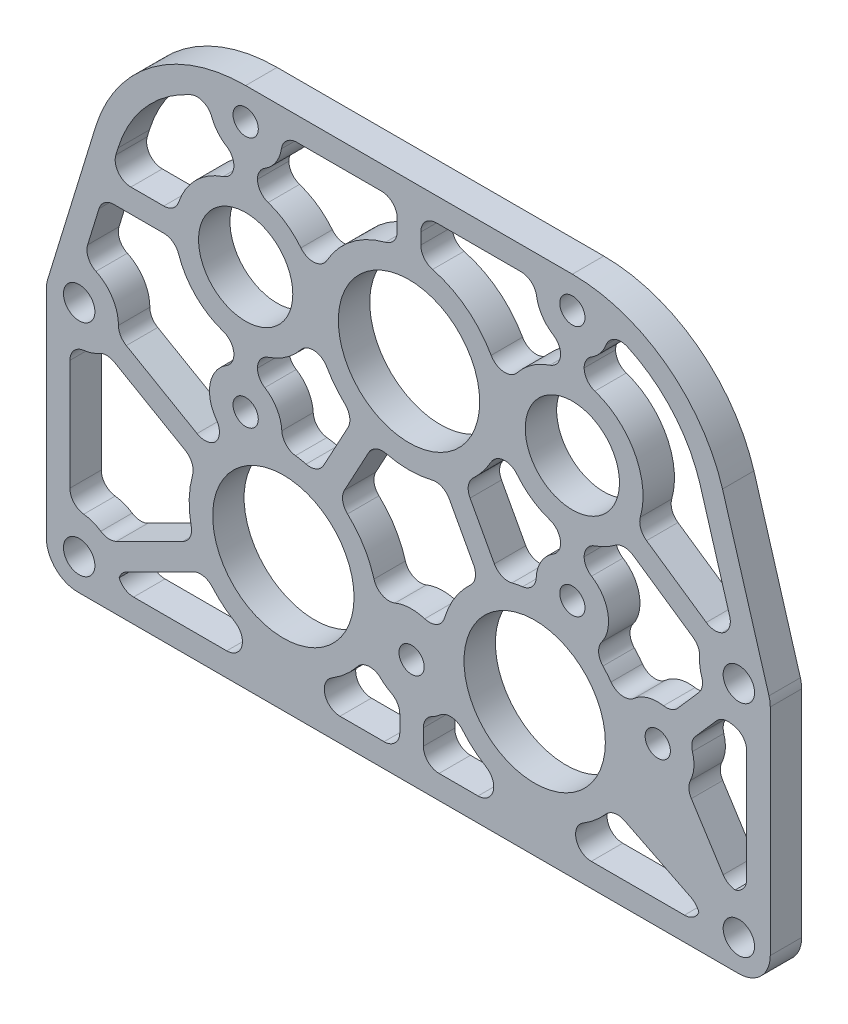
SolidWorks part; units mm, degrees
material "6061 Alloy"
ref_plane "Front Plane" through (0, 0, 0) normal (0, 0, 1) x (1, 0, 0)
ref_plane "Top Plane" through (0, 0, 0) normal (0, 1, 0) x (1, 0, 0)
ref_plane "Right Plane" through (0, 0, 0) normal (1, 0, 0) x (0, 0, -1)
sketch "Sketch1" plane through (0, 0, 0) normal (0, 0, 1) x (1, 0, 0)
  line L0 (0, 0) -> (-28088.6063, 0) construction
  line L1 (0, 0) -> (0, -28088.6063) construction
  line L2 (1.5394, 46.9041) -> (-37.2217, 46.9041) construction
  line L3 (50.8, 0) -> (50.8, 50000) construction
  line L4 (-7.62, 72.3041) -> (-7.62, 21.5041) construction
  line L5 (58.42, 72.3041) -> (58.42, 21.5041) construction
  line L6 (-110.2422, 36.5125) -> (49889.7578, 36.5125) construction
  line L7 (-115.6814, -26.9875) -> (-47.9173, -26.9875) construction
  line L8 (25.9168, -5.0978) -> (75.6832, 5.0978) construction
  line L9 (-110.2422, 33.3375) -> (49889.7578, 33.3375) construction
  line L10 (-41.275, 23.8125) -> (92.075, 23.8125) construction
  line L11 (-41.275, 23.8125) -> (-41.275, -20.6375) construction
  line L12 (92.075, 23.8125) -> (92.075, -20.6375) construction
  line L13 (-41.275, -20.6375) -> (92.075, -20.6375) construction
  line L15 (-47.9173, -26.9875) -> (98.425, -26.9875)
  line L16 (-37.973, 56.2184) -> (-47.9173, 23.8125)
  line L17 (-47.9173, 23.8125) -> (-47.9173, -26.9875)
  line L18 (98.425, 23.8125) -> (98.425, -26.9875)
  line L20 (-7.62, 78.6541) -> (58.42, 78.6541)
  line L21 (98.425, 23.8125) -> (88.773, 56.2184)
  line L25 (-47.9173, -26.9875) -> (98.425, -26.9875) construction
  circle A0 centre (0, 0) radius 14.2875
  circle A1 centre (50.8, 0) radius 14.2875
  circle A2 centre (25.4, 46.9041) radius 14.2875
  circle A3 centre (0, 0) radius 34.29 construction
  circle A4 centre (50.8, 0) radius 16.51 construction
  circle A5 centre (50.8, 0) radius 38.1 construction
  circle A6 centre (25.4, 46.9041) radius 25.4 construction
  circle A7 centre (-7.62, 46.9041) radius 7.62 construction
  circle A8 centre (58.42, 46.9041) radius 7.62 construction
  circle A9 centre (-7.62, 72.3041) radius 2.5527
  circle A10 centre (-7.62, 21.5041) radius 2.5527
  circle A11 centre (58.42, 72.3041) radius 2.5527
  circle A12 centre (58.42, 21.5041) radius 2.5527
  circle A13 centre (-7.62, 46.9041) radius 31.75 construction
  circle A14 centre (58.42, 46.9041) radius 31.75 construction
  circle A15 centre (58.42, 46.9041) radius 9.525
  circle A16 centre (-7.62, 46.9041) radius 9.525
  circle A17 centre (75.6832, 5.0978) radius 2.5527
  circle A18 centre (25.9168, -5.0978) radius 2.5527
  circle A19 centre (-41.275, 23.8125) radius 3.175
  circle A20 centre (92.075, 23.8125) radius 3.175
  circle A21 centre (-41.275, -20.6375) radius 3.175
  circle A22 centre (92.075, -20.6375) radius 3.175
  circle A23 centre (92.075, 23.8125) radius 6.35 construction
  circle A24 centre (50.8, 0) radius 39.37 construction
  circle A25 centre (-41.275, 23.8125) radius 6.35 construction
  circle A26 centre (-41.275, -20.6375) radius 6.35 construction
  circle A27 centre (92.075, -20.6375) radius 6.35 construction
  arc A28 (58.42, 78.6541) -> (88.773, 56.2184) centre (58.42, 46.9041) cw
  arc A29 (-37.973, 56.2184) -> (-7.62, 78.6541) centre (-7.62, 46.9041) cw
  circle A30 centre (25.4, 46.9041) radius 15.24 construction
  dimension "D1" = 28.575
  dimension "D2" = 68.58
  dimension "D3" = 33.02
  dimension "D4" = 76.2
  dimension "D5" = 50.8
  dimension "D6" = 15.24
  dimension "D10" = 5.1054
  dimension "D11" = 63.5
  dimension "D12" = 19.05
  dimension "D16" = 5.1054
  dimension "D18" = 6.35
  dimension "D25" = 12.7
  dimension "D26" = 78.74
  dimension "D27" = 30.48
  dimension "D7" = 25.4
  dimension "D8" = 50.8
  dimension "D9" = 25.4
  dimension "D13" = 36.5125
  dimension "D14" = 26.9875
  dimension "D15" = 50.8
  dimension "D17" = 5.0978
  dimension "D21" = 41.275
  dimension "D22" = 9.525
  dimension "D20" = 41.275
  dimension "D23" = 6.35
  dimension "D19" = 3.175
extrude "Boss-Extrude2" add sketch "Sketch1" along normal blind 6.35
fillet "Fillet1" radius 6.35 2 edges at (98.425, -26.9875, 3.175) (-47.9173, -26.9875, 3.175)
sketch "Sketch3" plane through (0, 0, 6.35) normal (0, 0, 1) x (1, 0, 0)
  line L0 (-7.62, 72.3041) -> (-7.62, 46.9041) construction
  line L1 (-7.62, 46.9041) -> (-7.62, 21.5041) construction
  line L2 (-7.62, 21.5041) -> (0, 0) construction
  line L3 (0, 0) -> (25.9168, -5.0978) construction
  line L4 (25.9168, -5.0978) -> (50.8, 0) construction
  line L5 (50.8, 0) -> (58.42, 21.5041) construction
  line L6 (58.42, 21.5041) -> (58.42, 46.9041) construction
  line L7 (58.42, 46.9041) -> (58.42, 72.3041) construction
  line L8 (0, 0) -> (25.4, 46.9041) construction
  line L9 (25.4, 46.9041) -> (50.8, 0) construction
  line L10 (25.4, 46.9041) -> (25.4, 73.8916) construction
  line L11 (58.42, 46.9041) -> (92.075, 23.8125) construction
  line L12 (92.075, 23.8125) -> (75.6832, 5.0978) construction
  line L13 (75.6832, 5.0978) -> (92.075, -20.6375) construction
  line L14 (25.9168, -5.0978) -> (25.9168, -22.225) construction
  line L15 (-41.275, 23.8125) -> (0, 0) construction
  line L16 (0, 0) -> (-41.275, -20.6375) construction
  line L17 (50.8, 0) -> (92.075, -20.6375) construction
  line L18 (23.5356, -5.0978) -> (23.5356, -22.225)
  line L19 (28.2981, -5.0978) -> (28.2981, -22.225)
  line L20 (-1.0649, 2.1299) -> (-42.3399, -18.5076)
  line L21 (-42.465, 21.7499) -> (-1.19, -2.0626)
  line L22 (2.0939, -1.1339) -> (27.4939, 45.7702)
  line L23 (23.3061, 45.7702) -> (48.7061, -1.1339)
  line L24 (27.7812, 46.9041) -> (27.7812, 73.8916)
  line L25 (60.8013, 21.5041) -> (60.8013, 46.9041)
  line L26 (-10.0013, 72.3041) -> (-10.0013, 46.9041)
  line L27 (-10.0013, 46.9041) -> (-10.0013, 21.5041)
  line L28 (60.8013, 46.9041) -> (60.8012, 72.3041)
  line L29 (57.0728, 44.9406) -> (90.7278, 21.849)
  line L30 (1.0649, -2.1299) -> (-40.2101, -22.7674)
  line L31 (-40.085, 25.8751) -> (1.19, 2.0626)
  line L32 (-2.0939, 1.1339) -> (23.3061, 48.038)
  line L33 (27.4939, 48.038) -> (52.8939, 1.1339)
  line L34 (23.0187, 46.9041) -> (23.0187, 73.8916)
  line L35 (56.0388, 21.5041) -> (56.0388, 46.9041)
  line L36 (-5.2388, 72.3041) -> (-5.2388, 46.9041)
  line L37 (-5.2388, 46.9041) -> (-5.2388, 21.5041)
  line L38 (56.0388, 46.9041) -> (56.0387, 72.3041)
  line L39 (59.7672, 48.8676) -> (93.4222, 25.776)
  line L40 (90.2837, 25.3815) -> (72.7158, 5.324)
  line L41 (-43.1548, 23.0982) -> (-43.1548, -20.6375)
  line L42 (-41.5673, -22.225) -> (92.075, -22.225)
  line L43 (93.6625, -20.6375) -> (93.6625, 23.1183)
  line L44 (93.6625, 23.1183) -> (84.2145, 54.8393)
  line L45 (58.42, 73.8916) -> (-7.62, 73.8916)
  line L46 (-33.4201, 54.8212) -> (-43.1548, 23.0982)
  line L47 (-43.1548, 23.0982) -> (-43.1548, -20.6375)
  line L48 (-41.5673, -22.225) -> (92.075, -22.225)
  line L49 (93.6625, -20.6375) -> (93.6625, 23.1183)
  line L50 (93.6625, 23.1183) -> (84.2145, 54.8393)
  line L51 (58.42, 73.8916) -> (-7.62, 73.8916)
  line L52 (-33.4201, 54.8212) -> (-43.1548, 23.0982)
  line L53 (72.7158, 5.324) -> (85.4443, -14.6599)
  line L54 (51.8649, 2.1299) -> (85.4443, -14.6599)
  line L55 (93.8663, 22.2435) -> (78.6505, 4.8715)
  line L56 (78.6505, 4.8715) -> (98.7057, -26.6151)
  line L57 (49.7351, -2.1299) -> (98.7057, -26.6151)
  line L58 (-7.62, 46.9041) -> (-35.8496, 46.9041) construction
  line L59 (-7.62, 49.2854) -> (-35.8496, 49.2854)
  line L60 (-7.62, 44.5229) -> (-39.3651, 44.5229)
  line L61 (-7.62, 44.5229) -> (-35.8496, 44.5229) construction
  circle A2 centre (-7.62, 72.3041) radius 7.3152
  circle A3 centre (-7.62, 72.3041) radius 7.3152
  circle A4 centre (58.42, 72.3041) radius 7.3152
  circle A5 centre (58.42, 72.3041) radius 7.3152
  circle A7 centre (-41.275, 23.8125) radius 7.9375
  circle A8 centre (-41.275, 23.8125) radius 7.9375
  circle A10 centre (-41.275, -20.6375) radius 7.9375
  circle A11 centre (-41.275, -20.6375) radius 7.9375
  circle A13 centre (92.075, -20.6375) radius 7.9375
  circle A14 centre (92.075, -20.6375) radius 7.9375
  circle A16 centre (92.075, 23.8125) radius 7.9375
  circle A17 centre (92.075, 23.8125) radius 7.9375
  circle A19 centre (-7.62, 46.9041) radius 14.2875
  circle A20 centre (-7.62, 46.9041) radius 14.2875
  circle A22 centre (25.4, 46.9041) radius 19.05
  circle A23 centre (25.4, 46.9041) radius 19.05
  circle A25 centre (58.42, 46.9041) radius 14.2875
  circle A26 centre (58.42, 46.9041) radius 14.2875
  arc A28 (-43.1548, -20.6375) -> (-41.5673, -22.225) centre (-41.5673, -20.6375) ccw
  arc A29 (92.075, -22.225) -> (93.6625, -20.6375) centre (92.075, -20.6375) ccw
  arc A30 (84.2145, 54.8393) -> (58.42, 73.8916) centre (58.42, 46.9041) ccw
  arc A31 (-7.62, 73.8916) -> (-33.4201, 54.8212) centre (-7.62, 46.9041) ccw
  arc A32 (-43.1548, -20.6375) -> (-41.5673, -22.225) centre (-41.5673, -20.6375) ccw
  arc A33 (92.075, -22.225) -> (93.6625, -20.6375) centre (92.075, -20.6375) ccw
  arc A34 (84.2145, 54.8393) -> (58.42, 73.8916) centre (58.42, 46.9041) ccw
  arc A35 (-7.62, 73.8916) -> (-33.4201, 54.8212) centre (-7.62, 46.9041) ccw
  circle A36 centre (58.42, 21.5041) radius 7.3152
  circle A37 centre (58.42, 21.5041) radius 7.3152
  circle A39 centre (-7.62, 21.5041) radius 7.3152
  circle A40 centre (-7.62, 21.5041) radius 7.3152
  circle A42 centre (0, 0) radius 19.05
  circle A43 centre (0, 0) radius 19.05
  circle A45 centre (25.9168, -5.0978) radius 8.9027
  circle A46 centre (25.9168, -5.0978) radius 8.9027
  circle A48 centre (50.8, 0) radius 19.05
  circle A49 centre (50.8, 0) radius 19.05
  circle A51 centre (75.6832, 5.0978) radius 7.3152
  circle A52 centre (75.6832, 5.0978) radius 7.3152
  dimension "D1" = 4.7625
  dimension "D2" = 4.7625
  dimension "D3" = 4.7625
  dimension "D4" = 4.7625
  dimension "D5" = 4.7625
  dimension "D6" = 4.7625
  dimension "D7" = 4.7625
  dimension "D8" = 4.7625
  dimension "D9" = 4.7625
  dimension "D10" = 4.7625
  dimension "D11" = 4.7625
  dimension "D12" = 4.7625
  dimension "D13" = 4.7625
  dimension "D14" = 6.35
  dimension "D15" = 4.7625
  dimension "D16" = 4.7625
  dimension "D17" = 2.3813
  dimension "D18" = 2.3813
  dimension "D19" = 2.3813
  dimension "D20" = 2.3813
  dimension "D21" = 2.3813
  dimension "D22" = 2.3813
  dimension "D23" = 2.3813
  dimension "D24" = 2.3813
extrude "Cut-Extrude3" cut sketch "Sketch3" against normal blind 10.795 contours A43 A40 L27 A20 L60 L52 A8 L31 | A3 A35 L52 L59 A20 L26 | A43 L21 A8 L47 A11 L20 | A46 A43 L30 A11 L48 L18 | A49 A46 L19 L48 A14 L57 | A49 L23 A23 L22 A43 A46 | A43 L32 A23 A20 L37 A40 | A23 L34 L51 A3 L36 A20 | A26 L38 A5 L51 L24 A23 | A49 A37 L35 A26 A23 L33 | L50 A34 A5 L28 A26 L39 A17 | A52 L40 A17 L29 A26 L25 A37 A49 | A52 L56 A14 L49 A17 L55 region at (22.9471, -17.9506, 6.35) region at (32.0195, -12.35, 6.35) region at (25.3759, 16.111, 6.35) region at (-32.1515, 1.2464, 6.35) region at (4.5834, 29.1568, 6.35) region at (88.8593, 2.4178, 6.35) region at (-24.8448, 30.0949, 6.35) region at (46.2166, 29.1568, 6.35) region at (-22.5827, 60.0097, 6.35) region at (8.446, 65.9004, 6.35) region at (72.5291, 22.7851, 6.35) region at (42.354, 65.9004, 6.35) region at (76.8138, 52.0076, 6.35)
fillet "Fillet3" radius 3.175 81 edges at (56.0388, 28.4209, 3.175) (56.0388, 32.8164, 3.175) (44.3141, 44.6331, 3.175) (36.4942, 31.418, 3.175) (43.8937, 17.754, 3.175) (51.5338, 19.0359, 3.175) (-14.9119, 72.8878, 3.175) (-10.0013, 65.3873, 3.175) (-10.0013, 60.9918, 3.175) (-21.7077, 49.2854, 3.175) (-35.1188, 49.2854, 3.175) (-40.5111, 31.7132, 3.175) (-36.5803, 44.5229, 3.175) (-21.7077, 44.5229, 3.175) (-10.0013, 32.8164, 3.175) (-10.0013, 28.4209, 3.175) (-11.4157, 15.2507, 3.175) (-15.1815, 11.5077, 3.175) (-33.5264, 22.0913, 3.175) (-43.1548, 16.1008, 3.175) (-35.9063, 17.9661, 3.175) (-17.9701, -6.3227, 3.175) (-17.5614, 7.3824, 3.175) (-33.4376, -19.3811, 3.175) (-43.1548, -12.9258, 3.175) (-35.5674, -15.1214, 3.175) (-33.4979, -22.225, 3.175) (-15.8403, -10.5825, 3.175) (17.4118, -7.7287, 3.175) (23.5356, -13.6761, 3.175) (23.5356, -22.225, 3.175) (28.2981, -22.225, 3.175) (28.2981, -13.6761, 3.175) (33.9621, -8.9099, 3.175) (66.6403, -10.5825, 3.175) (84.2376, -19.3811, 3.175) (84.2979, -22.225, 3.175) (93.6625, -12.8604, 3.175) (90.0157, -12.9718, 3.175) (82.0318, 8.732, 3.175) (81.4075, 0.5431, 3.175) (88.8773, 16.5476, 3.175) (93.6625, 16.0354, 3.175) (84.4842, 26.1329, 3.175) (85.2947, 19.6855, 3.175) (78.4492, 11.8699, 3.175) (68.5789, 6.8419, 3.175) (62.2157, 15.2507, 3.175) (60.8013, 28.4209, 3.175) (60.8013, 32.8164, 3.175) (68.6891, 36.9704, 3.175) (87.1787, 30.0599, 3.175) (91.1092, 31.691, 3.175) (71.3835, 40.8974, 3.175) (65.7119, 72.8878, 3.175) (60.8013, 60.9918, 3.175) (60.8013, 65.3873, 3.175) (51.2791, 73.8916, 3.175) (56.0388, 65.3873, 3.175) (56.0388, 60.9918, 3.175) (44.3141, 49.1751, 3.175) (27.7812, 65.8047, 3.175) (27.7812, 73.8916, 3.175) (23.0187, 65.8047, 3.175) (23.0187, 73.8916, 3.175) (-0.4791, 73.8916, 3.175) (-5.2388, 65.3873, 3.175) (-5.2388, 60.9918, 3.175) (6.4859, 49.1751, 3.175) (39.7058, 15.4862, 3.175) (31.8149, 1.5709, 3.175) (19.0418, 0.5584, 3.175) (11.0942, 15.4862, 3.175) (32.3063, 29.1501, 3.175) (18.4937, 29.1501, 3.175) (6.9063, 17.754, 3.175) (-0.7338, 19.0359, 3.175) (14.3058, 31.418, 3.175) (-5.2388, 28.4209, 3.175) (-5.2388, 32.8164, 3.175) (6.4859, 44.6331, 3.175)
sketch "Sketch7" plane through (0, 0, 6.35) normal (0, 0, 1) x (1, 0, 0)
  line L0 (31.4731, -22.225) -> (81.0765, -22.225) construction
  line L3 (-30.2765, -22.225) -> (20.3606, -22.225) construction
  line L4 (-11.4476, -22.225) -> (11.4476, -22.225)
  line L5 (62.2476, -22.225) -> (39.3524, -22.225)
  arc A0 (-11.4476, -22.225) -> (-9.8123, -16.3286) centre (-11.4476, -19.05) ccw
  arc A1 (9.8123, -16.3286) -> (11.4476, -22.225) centre (11.4476, -19.05) ccw
  arc A2 (-14.3679, -12.5086) -> (14.9774, -11.772) centre (0, 0) ccw construction
  arc A3 (-9.8123, -16.3286) -> (9.8123, -16.3286) centre (0, 0) ccw
  arc A4 (60.6123, -16.3286) -> (40.9878, -16.3286) centre (50.8, 0) cw
  arc A5 (40.9878, -16.3286) -> (39.3524, -22.225) centre (39.3524, -19.05) cw
  arc A6 (62.2476, -22.225) -> (60.6123, -16.3286) centre (62.2476, -19.05) cw
  arc A7 (36.2001, -12.237) -> (65.1679, -12.5086) centre (50.8, 0) ccw construction
  dimension "D1" = 6.35
  dimension "D2" = 3.175
  dimension "D3" = 3.175
extrude "Boss-Extrude3" add sketch "Sketch7" against normal up to surface (6.35 mm away) up to face at (74.4946, 51.6759, 0)
fillet "Fillet4" radius 6.35 2 edges at (98.425, 23.8125, 3.175) (-47.9173, 23.8125, 3.175)
equation "\"D2@Sketch1\"=54/20"
equation "\"D3@Sketch1\"=26/20"
equation "\"D4@Sketch1\"=60/20"
equation "\"D5@Sketch1\"=40/20"
equation "\"D6@Sketch1\"=12/20"
equation "\"D9@Sketch1\"=\"D8@Sketch1\"/2"
equation "\"D20@Sketch1\"=\"D21@Sketch1\""
